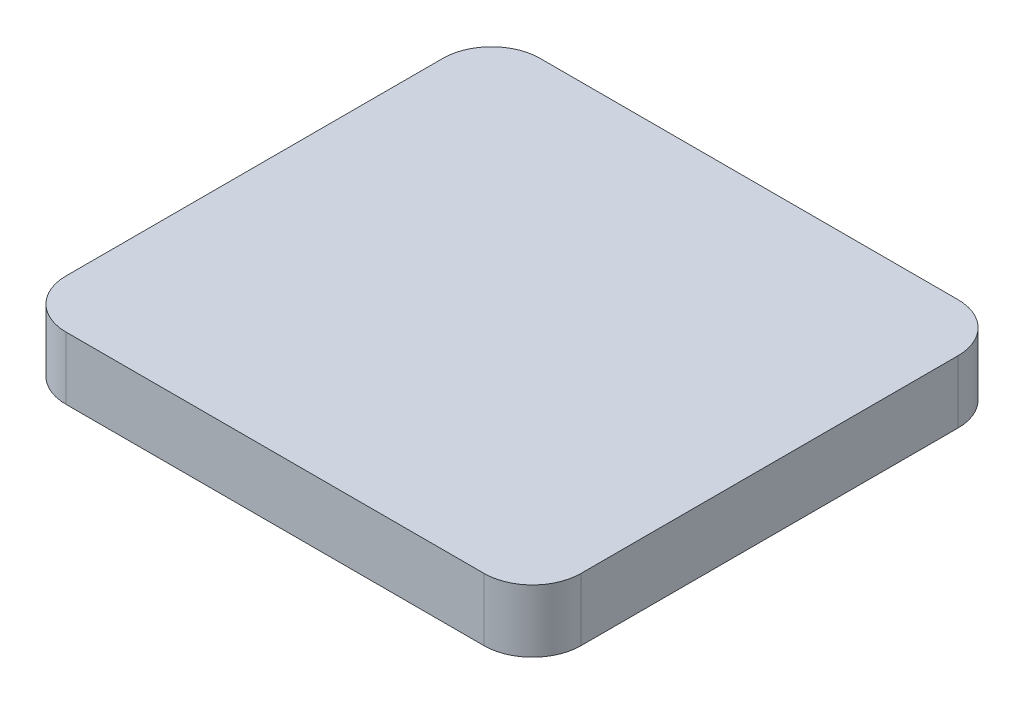
SolidWorks part; units mm, degrees
ref_plane "Front Plane" through (0, 0, 0) normal (0, 0, 1) x (1, 0, 0)
ref_plane "Top Plane" through (0, 0, 0) normal (0, 1, 0) x (1, 0, 0)
ref_plane "Right Plane" through (0, 0, 0) normal (1, 0, 0) x (0, 0, -1)
sketch "Sketch1" plane through (0, 0, 0) normal (0, 1, 0) x (1, 0, 0)
  line L0 (-21.85, 19.95) -> (-21.85, 21.95) construction
  line L1 (19.35, 19.95) -> (-19.35, 19.95)
  line L2 (21.85, 17.45) -> (21.85, -17.45)
  line L3 (19.35, -19.95) -> (-19.35, -19.95)
  line L4 (-21.85, 17.45) -> (-21.85, -17.45)
  line L5 (21.85, 19.95) -> (-21.85, -19.95) construction
  line L6 (21.85, -19.95) -> (-21.85, 19.95) construction
  line L7 (23.85, -21.95) -> (-23.85, -21.95)
  line L8 (23.85, -21.95) -> (23.85, 21.95)
  line L9 (23.85, 21.95) -> (-23.85, 21.95)
  line L10 (-23.85, -21.95) -> (-23.85, 21.95)
  line L11 (23.85, -21.95) -> (-23.85, 21.95) construction
  line L12 (23.85, 21.95) -> (-23.85, -21.95) construction
  line L13 (-21.85, 19.95) -> (-23.85, 19.95) construction
  arc A0 (-19.35, -19.95) -> (-21.85, -17.45) centre (-19.35, -17.45) cw
  arc A1 (21.85, -17.45) -> (19.35, -19.95) centre (19.35, -17.45) cw
  arc A2 (19.35, 19.95) -> (21.85, 17.45) centre (19.35, 17.45) cw
  arc A3 (-19.35, 19.95) -> (-21.85, 17.45) centre (-19.35, 17.45) ccw
  circle A4 centre (-19.35, 17.45) radius 4.5
  circle A5 centre (19.35, 17.45) radius 4.5
  circle A6 centre (19.35, -17.45) radius 4.5
  circle A7 centre (-19.35, -17.45) radius 4.5
  point P0 (0, 0)
  point P6 (0, 0)
  dimension "D4" = 2.5
  dimension "D1" = 43.7
  dimension "D2" = 39.9
  dimension "D3" = 2
extrude "Boss-Extrude1" add sketch "Sketch1" along normal blind 1.3 contours L1 A4 L4 A3 | A7 L4 A4 L10 | A7 L3 A0 L4 | A7 L7 A6 L3 | A6 L2 A1 L3 | A6 L8 A5 L2 | L2 A5 L1 A2 | A5 L9 A4 L1 region at (17.4792, 0, -20.0666) region at (0, 0, -20.9787) region at (-17.4792, 0, -20.0666) region at (22.8824, 0, 0) region at (23.2158, 0, 15.3836) region at (-22.8824, 0, 0) region at (0, 0, 20.9787) region at (-21.9666, 0, 15.5792)
sketch "Sketch2" plane through (0, 1.3, 0) normal (0, 1, 0) x (1, 0, 0)
  line L4 (-19.35, -21.95) -> (19.35, -21.95)
  line L5 (23.85, -17.45) -> (23.85, 17.45)
  line L6 (19.35, 21.95) -> (-19.35, 21.95)
  line L7 (-23.85, 17.45) -> (-23.85, -17.45)
  line L8 (-19.35, -21.95) -> (19.35, -21.95)
  line L9 (23.85, -17.45) -> (23.85, 17.45)
  line L10 (19.35, 21.95) -> (-19.35, 21.95)
  line L11 (-23.85, 17.45) -> (-23.85, -17.45)
  arc A4 (19.35, -21.95) -> (23.85, -17.45) centre (19.35, -17.45) ccw
  arc A5 (23.85, 17.45) -> (19.35, 21.95) centre (19.35, 17.45) ccw
  arc A6 (-19.35, 21.95) -> (-23.85, 17.45) centre (-19.35, 17.45) ccw
  arc A7 (-23.85, -17.45) -> (-19.35, -21.95) centre (-19.35, -17.45) ccw
  arc A8 (19.35, -21.95) -> (23.85, -17.45) centre (19.35, -17.45) ccw
  arc A9 (23.85, 17.45) -> (19.35, 21.95) centre (19.35, 17.45) ccw
  arc A10 (-19.35, 21.95) -> (-23.85, 17.45) centre (-19.35, 17.45) ccw
  arc A11 (-23.85, -17.45) -> (-19.35, -21.95) centre (-19.35, -17.45) ccw
  dimension "D1" = 0
extrude "Boss-Extrude2" add sketch "Sketch2" along normal blind 1.5
sketch "Sketch3" plane through (0, 1.3, 0) normal (0, -1, 0) x (1, 0, 0)
  line L0 (-23.85, 0) -> (23.85, 0) construction
  line L1 (-23.85, 17.45) -> (-23.85, -17.45) construction
  line L2 (23.85, 17.45) -> (23.85, -17.45) construction
  line L3 (-23.85, 10.975) -> (23.85, 10.975) construction
  line L4 (0, 10.975) -> (0, 21.95) construction
  line L5 (19.35, 21.95) -> (-19.35, 21.95) construction
  line L6 (0, 10.975) -> (0, 0) construction
  line L7 (-23.85, -10.975) -> (23.85, -10.975) construction
  line L8 (0, 0) -> (4.1348, 4.1348) construction
  line L9 (10.975, -23.85) -> (10.975, 23.85) construction
  line L10 (-10.975, -23.85) -> (-10.975, 23.85) construction
  line L11 (-21.85, -17.45) -> (-21.85, 17.45) construction
  line L12 (-21.85, -17.45) -> (-21.85, 17.45) construction
  line L13 (19.35, -19.95) -> (-19.35, -19.95) construction
  line L14 (21.85, -17.45) -> (21.85, 17.45) construction
  line L15 (19.35, 19.95) -> (-19.35, 19.95) construction
  line L16 (19.35, 19.95) -> (-19.35, 19.95) construction
  circle A0 centre (-21.85, 10.975) radius 0.4
  circle A1 centre (-21.85, 0) radius 0.4
  circle A2 centre (-21.85, -10.975) radius 0.4
  circle A3 centre (-10.975, -19.95) radius 0.4
  circle A4 centre (10.975, -19.95) radius 0.4
  circle A5 centre (21.85, -10.975) radius 0.4
  circle A6 centre (21.85, 0) radius 0.4
  circle A7 centre (21.85, 10.975) radius 0.4
  circle A8 centre (10.975, 19.95) radius 0.4
  circle A9 centre (0, 19.95) radius 0.4
  circle A10 centre (-10.975, 19.95) radius 0.4
  point P56 (-21.6, 0)
  point P57 (21.6, -10.85)
  dimension "D2" = 0.8
  dimension "D1" = 45
extrude "Boss-Extrude3" add sketch "Sketch3" along normal up to surface (1.3 mm away) up to face at (0, 0, 0)
sketch "Sketch4" plane through (0, 0, 0) normal (0, -1, 0) x (1, 0, 0)
  line L0 (-22.85, 17.45) -> (-22.85, -17.45)
  line L1 (-19.35, -20.95) -> (19.35, -20.95)
  line L2 (22.85, -17.45) -> (22.85, 17.45)
  line L3 (19.35, 20.95) -> (-19.35, 20.95)
  line L4 (19.35, 21.95) -> (-19.35, 21.95)
  line L5 (-23.85, 17.45) -> (-23.85, -17.45)
  line L6 (-19.35, -21.95) -> (19.35, -21.95)
  line L7 (23.85, -17.45) -> (23.85, 17.45)
  line L8 (19.35, 21.95) -> (-19.35, 21.95)
  line L9 (-23.85, 17.45) -> (-23.85, -17.45)
  line L10 (-19.35, -21.95) -> (19.35, -21.95)
  line L11 (23.85, -17.45) -> (23.85, 17.45)
  arc A0 (-19.35, 20.95) -> (-22.85, 17.45) centre (-19.35, 17.45) ccw
  arc A1 (-22.85, -17.45) -> (-19.35, -20.95) centre (-19.35, -17.45) ccw
  arc A2 (19.35, -20.95) -> (22.85, -17.45) centre (19.35, -17.45) ccw
  arc A3 (22.85, 17.45) -> (19.35, 20.95) centre (19.35, 17.45) ccw
  arc A4 (-19.35, 21.95) -> (-23.85, 17.45) centre (-19.35, 17.45) ccw
  arc A5 (-23.85, -17.45) -> (-19.35, -21.95) centre (-19.35, -17.45) ccw
  arc A6 (19.35, -21.95) -> (23.85, -17.45) centre (19.35, -17.45) ccw
  arc A7 (23.85, 17.45) -> (19.35, 21.95) centre (19.35, 17.45) ccw
  arc A8 (-19.35, 21.95) -> (-23.85, 17.45) centre (-19.35, 17.45) ccw
  arc A9 (-23.85, -17.45) -> (-19.35, -21.95) centre (-19.35, -17.45) ccw
  arc A10 (19.35, -21.95) -> (23.85, -17.45) centre (19.35, -17.45) ccw
  arc A11 (23.85, 17.45) -> (19.35, 21.95) centre (19.35, 17.45) ccw
  dimension "D1" = 0
  dimension "D2" = 1
extrude "Boss-Extrude4" add sketch "Sketch4" along normal blind 3
sketch "Sketch5" plane through (0, 1.3, 0) normal (0, -1, 0) x (1, 0, 0)
  line L31 (-11.9548, 18.95) -> (-19.35, 18.95)
  line L32 (-20.85, 17.45) -> (-20.85, 11.9548)
  line L33 (-20.85, 9.9952) -> (-20.85, 0.9798)
  line L34 (-20.85, -0.9798) -> (-20.85, -9.9952)
  line L35 (-20.85, -11.9548) -> (-20.85, -17.45)
  line L36 (-19.35, -18.95) -> (-11.9548, -18.95)
  line L37 (-9.9952, -18.95) -> (9.9952, -18.95)
  line L38 (11.9548, -18.95) -> (19.35, -18.95)
  line L39 (20.85, -17.45) -> (20.85, -11.9548)
  line L40 (20.85, -9.9952) -> (20.85, -0.9798)
  line L41 (20.85, 0.9798) -> (20.85, 9.9952)
  line L42 (20.85, 11.9548) -> (20.85, 17.45)
  line L43 (19.35, 18.95) -> (11.9548, 18.95)
  line L44 (9.9952, 18.95) -> (0.9798, 18.95)
  line L45 (-0.9798, 18.95) -> (-9.9952, 18.95)
  line L46 (-11.9548, 18.95) -> (-19.35, 18.95)
  line L47 (-20.85, 17.45) -> (-20.85, 11.9548)
  line L48 (-20.85, 9.9952) -> (-20.85, 0.9798)
  line L49 (-20.85, -0.9798) -> (-20.85, -9.9952)
  line L50 (-20.85, -11.9548) -> (-20.85, -17.45)
  line L51 (-19.35, -18.95) -> (-11.9548, -18.95)
  line L52 (-9.9952, -18.95) -> (9.9952, -18.95)
  line L53 (11.9548, -18.95) -> (19.35, -18.95)
  line L54 (20.85, -17.45) -> (20.85, -11.9548)
  line L55 (20.85, -9.9952) -> (20.85, -0.9798)
  line L56 (20.85, 0.9798) -> (20.85, 9.9952)
  line L57 (20.85, 11.9548) -> (20.85, 17.45)
  line L58 (19.35, 18.95) -> (11.9548, 18.95)
  line L59 (9.9952, 18.95) -> (0.9798, 18.95)
  line L60 (-0.9798, 18.95) -> (-9.9952, 18.95)
  arc A30 (-11.9548, 18.95) -> (-9.9952, 18.95) centre (-10.975, 19.95) ccw
  arc A31 (-19.35, 18.95) -> (-20.85, 17.45) centre (-19.35, 17.45) ccw
  arc A32 (-20.85, 9.9952) -> (-20.85, 11.9548) centre (-21.85, 10.975) ccw
  arc A33 (-20.85, -0.9798) -> (-20.85, 0.9798) centre (-21.85, 0) ccw
  arc A34 (-20.85, -11.9548) -> (-20.85, -9.9952) centre (-21.85, -10.975) ccw
  arc A35 (-20.85, -17.45) -> (-19.35, -18.95) centre (-19.35, -17.45) ccw
  arc A36 (-9.9952, -18.95) -> (-11.9548, -18.95) centre (-10.975, -19.95) ccw
  arc A37 (11.9548, -18.95) -> (9.9952, -18.95) centre (10.975, -19.95) ccw
  arc A38 (19.35, -18.95) -> (20.85, -17.45) centre (19.35, -17.45) ccw
  arc A39 (20.85, -9.9952) -> (20.85, -11.9548) centre (21.85, -10.975) ccw
  arc A40 (20.85, 0.9798) -> (20.85, -0.9798) centre (21.85, 0) ccw
  arc A41 (20.85, 11.9548) -> (20.85, 9.9952) centre (21.85, 10.975) ccw
  arc A42 (20.85, 17.45) -> (19.35, 18.95) centre (19.35, 17.45) ccw
  arc A43 (9.9952, 18.95) -> (11.9548, 18.95) centre (10.975, 19.95) ccw
  arc A44 (-0.9798, 18.95) -> (0.9798, 18.95) centre (0, 19.95) ccw
  arc A45 (-11.9548, 18.95) -> (-9.9952, 18.95) centre (-10.975, 19.95) ccw
  arc A46 (-19.35, 18.95) -> (-20.85, 17.45) centre (-19.35, 17.45) ccw
  arc A47 (-20.85, 9.9952) -> (-20.85, 11.9548) centre (-21.85, 10.975) ccw
  arc A48 (-20.85, -0.9798) -> (-20.85, 0.9798) centre (-21.85, 0) ccw
  arc A49 (-20.85, -11.9548) -> (-20.85, -9.9952) centre (-21.85, -10.975) ccw
  arc A50 (-20.85, -17.45) -> (-19.35, -18.95) centre (-19.35, -17.45) ccw
  arc A51 (-9.9952, -18.95) -> (-11.9548, -18.95) centre (-10.975, -19.95) ccw
  arc A52 (11.9548, -18.95) -> (9.9952, -18.95) centre (10.975, -19.95) ccw
  arc A53 (19.35, -18.95) -> (20.85, -17.45) centre (19.35, -17.45) ccw
  arc A54 (20.85, -9.9952) -> (20.85, -11.9548) centre (21.85, -10.975) ccw
  arc A55 (20.85, 0.9798) -> (20.85, -0.9798) centre (21.85, 0) ccw
  arc A56 (20.85, 11.9548) -> (20.85, 9.9952) centre (21.85, 10.975) ccw
  arc A57 (20.85, 17.45) -> (19.35, 18.95) centre (19.35, 17.45) ccw
  arc A58 (9.9952, 18.95) -> (11.9548, 18.95) centre (10.975, 19.95) ccw
  arc A59 (-0.9798, 18.95) -> (0.9798, 18.95) centre (0, 19.95) ccw
  dimension "D1" = 1
extrude "Cut-Extrude1" cut sketch "Sketch5" against normal blind 0.5
